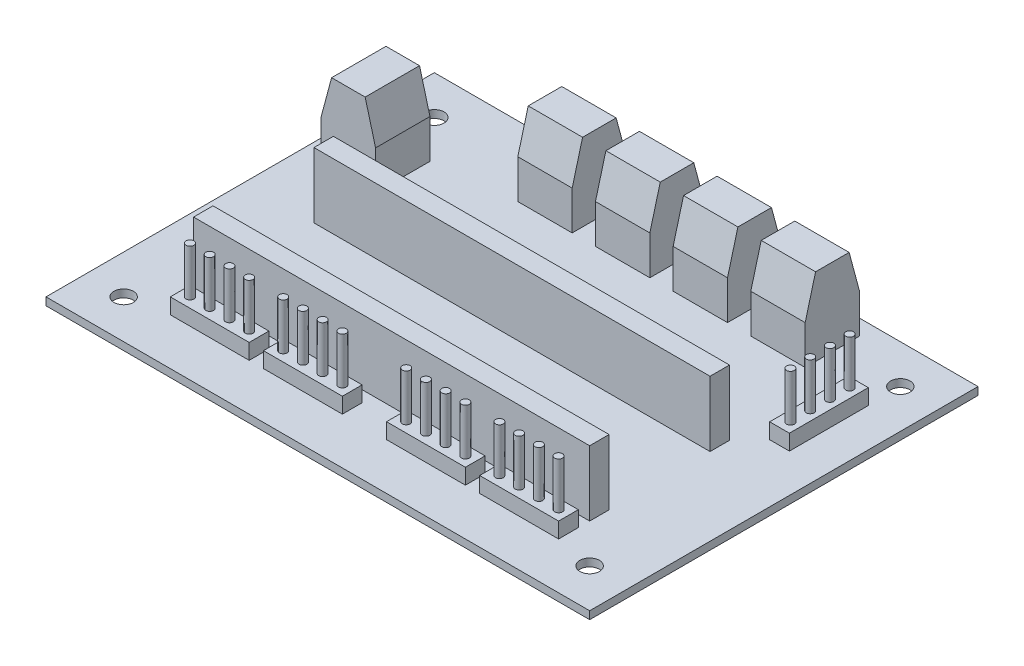
SolidWorks part; units mm, degrees
material "ABS"
ref_plane "Спереди" through (0, 0, 0) normal (0, 0, 1) x (1, 0, 0)
ref_plane "Сверху" through (0, 0, 0) normal (0, 1, 0) x (1, 0, 0)
ref_plane "Справа" through (0, 0, 0) normal (1, 0, 0) x (0, 0, -1)
sketch "Эскиз2" plane through (0, 0, 0) normal (0, 1, 0) x (1, 0, 0)
  line L0 (0, 25) -> (113.3637, 25) construction
  line L1 (0, 0) -> (70, 0)
  line L2 (0, 0) -> (0, 50)
  line L3 (0, 50) -> (70, 50)
  line L4 (70, 0) -> (70, 50)
  line L5 (35, 50) -> (35, -7.1391) construction
  circle A0 centre (5, 45) radius 1.25
  circle A1 centre (65, 45) radius 1.25
  circle A2 centre (65, 5) radius 1.25
  circle A3 centre (5, 5) radius 1.25
  dimension "D3" = 2.5
  dimension "D1" = 70
  dimension "D2" = 50
  dimension "D4" = 5
  dimension "D5" = 5
extrude "Бобышка-Вытянуть1" add sketch "Эскиз2" along normal blind 1
sketch "Эскиз3" plane through (0, 1, 0) normal (0, 1, 0) x (1, 0, 0)
  line L0 (0, 0) -> (70, 0) construction
  line L1 (9, 12.5) -> (60, 12.5)
  line L2 (9, 12.5) -> (9, 10)
  line L3 (9, 10) -> (60, 10)
  line L4 (60, 12.5) -> (60, 10)
  line L9 (70, 0) -> (70, 50) construction
  line L10 (60, 12.5) -> (60, 19) construction
  line L11 (60, 19) -> (7.0253, 19) construction
  line L12 (9, 28) -> (60, 28)
  line L13 (60, 25.5) -> (60, 28)
  line L14 (9, 25.5) -> (60, 25.5)
  line L15 (9, 25.5) -> (9, 28)
  dimension "D1" = 2.5
  dimension "D2" = 51
  dimension "D6" = 10
  dimension "D7" = 10
extrude "Бобышка-Вытянуть2" add sketch "Эскиз3" along normal blind 8.4
sketch "Эскиз4" plane through (0, 1, 0) normal (0, 1, 0) x (1, 0, 0)
  line L0 (70, 0) -> (70, 50) construction
  line L1 (60, 8.54) -> (49.84, 8.54)
  line L2 (60, 8.54) -> (60, 6)
  line L3 (60, 6) -> (49.84, 6)
  line L4 (49.84, 8.54) -> (49.84, 6)
  line L5 (0, 0) -> (70, 0) construction
  line L6 (48, 8.54) -> (48, 6)
  line L7 (35, 0) -> (35, 38.4524) construction
  line L8 (48, 8.54) -> (37.84, 8.54)
  line L9 (37.84, 8.54) -> (37.84, 6)
  line L10 (48, 6) -> (37.84, 6)
  line L11 (10, 6) -> (20.16, 6)
  line L12 (20.16, 8.54) -> (20.16, 6)
  line L13 (10, 8.54) -> (20.16, 8.54)
  line L14 (10, 8.54) -> (10, 6)
  line L15 (22, 8.54) -> (32.16, 8.54)
  line L16 (32.16, 8.54) -> (32.16, 6)
  line L17 (22, 6) -> (32.16, 6)
  line L18 (22, 8.54) -> (22, 6)
  line L19 (62.5185, 40.8177) -> (62.5185, 30.6577)
  line L20 (62.5185, 40.8177) -> (65.0585, 40.8177)
  line L21 (65.0585, 40.8177) -> (65.0585, 30.6577)
  line L22 (62.5185, 30.6577) -> (65.0585, 30.6577)
  dimension "D1" = 2.54
  dimension "D2" = 10.16
  dimension "D3" = 10
  dimension "D4" = 6
  dimension "D5" = 2
extrude "Бобышка-Вытянуть3" add sketch "Эскиз4" along normal blind 2
sketch "Эскиз5" plane through (0, 3, 0) normal (0, 1, 0) x (1, 0, 0)
  line L0 (60, 6) -> (60, 8.54) construction
  line L1 (49.84, 6) -> (60, 6) construction
  line L2 (35, 0) -> (35, 20.127) construction
  line L3 (0, 0) -> (70, 0) construction
  circle A0 centre (58.73, 7.27) radius 0.5
  circle A1 centre (56.19, 7.27) radius 0.5
  circle A2 centre (53.65, 7.27) radius 0.5
  circle A3 centre (51.11, 7.27) radius 0.5
  circle A4 centre (46.73, 7.27) radius 0.5
  circle A5 centre (44.19, 7.27) radius 0.5
  circle A6 centre (41.65, 7.27) radius 0.5
  circle A7 centre (39.11, 7.27) radius 0.5
  circle A8 centre (25.81, 7.27) radius 0.5
  circle A9 centre (11.27, 7.27) radius 0.5
  circle A10 centre (13.81, 7.27) radius 0.5
  circle A11 centre (16.35, 7.27) radius 0.5
  circle A12 centre (18.89, 7.27) radius 0.5
  circle A13 centre (23.27, 7.27) radius 0.5
  circle A14 centre (28.35, 7.27) radius 0.5
  circle A15 centre (30.89, 7.27) radius 0.5
  circle A16 centre (63.8839, 31.9731) radius 0.5
  circle A17 centre (63.8839, 34.5131) radius 0.5
  circle A18 centre (63.8839, 37.0531) radius 0.5
  circle A19 centre (63.8839, 39.5931) radius 0.5
  dimension "D1" = 1
  dimension "D2" = 1.27
  dimension "D3" = 1.27
  dimension "D4" = 4
  dimension "D5" = 2
  dimension "D6" = 4
extrude "Бобышка-Вытянуть4" add sketch "Эскиз5" along normal blind 6
sketch "Эскиз6" plane through (0, 1, 0) normal (0, 1, 0) x (1, 0, 0)
  line L0 (19.7472, 48.0002) -> (26.7472, 48.0002)
  line L5 (2.608, 39.8256) -> (9.608, 39.8256)
  line L6 (2.608, 39.8256) -> (2.608, 32.8256)
  line L7 (2.608, 32.8256) -> (9.608, 32.8256)
  line L8 (9.608, 39.8256) -> (9.608, 32.8256)
  line L9 (19.7472, 48.0002) -> (19.7472, 41.0002)
  line L10 (19.7472, 41.0002) -> (26.7472, 41.0002)
  line L11 (26.7472, 48.0002) -> (26.7472, 41.0002)
  line L12 (29.7472, 48.0002) -> (36.7472, 48.0002)
  line L13 (36.7472, 48.0002) -> (36.7472, 41.0002)
  line L14 (29.7472, 41.0002) -> (36.7472, 41.0002)
  line L15 (29.7472, 48.0002) -> (29.7472, 41.0002)
  line L16 (39.7472, 48.0002) -> (46.7472, 48.0002)
  line L17 (46.7472, 48.0002) -> (46.7472, 41.0002)
  line L18 (39.7472, 41.0002) -> (46.7472, 41.0002)
  line L19 (39.7472, 48.0002) -> (39.7472, 41.0002)
  line L20 (49.7472, 48.0002) -> (56.7472, 48.0002)
  line L21 (56.7472, 48.0002) -> (56.7472, 41.0002)
  line L22 (49.7472, 41.0002) -> (56.7472, 41.0002)
  line L23 (49.7472, 48.0002) -> (49.7472, 41.0002)
  dimension "D1" = 7
  dimension "D2" = 7
  dimension "D3" = 4
extrude "Бобышка-Вытянуть5" add sketch "Эскиз6" along normal blind 10
chamfer "Фаска1" distance 5 angle 15 10 edges at (53.2472, 11, -48.0002) (53.2472, 11, -41.0002) (43.2472, 11, -48.0002) (43.2472, 11, -41.0002) (33.2472, 11, -41.0002) (33.2472, 11, -48.0002) (23.2472, 11, -48.0002) (23.2472, 11, -41.0002) (9.608, 11, -36.3256) (2.608, 11, -36.3256) first distance on face at (53.2472, 6, -48.0002) first distance on face at (53.2472, 6, -41.0002) first distance on face at (43.2472, 6, -48.0002) first distance on face at (43.2472, 6, -41.0002) first distance on face at (33.2472, 6, -41.0002) first distance on face at (33.2472, 6, -48.0002) first distance on face at (23.2472, 6, -48.0002) first distance on face at (23.2472, 6, -41.0002) first distance on face at (9.608, 6, -36.3256) first distance on face at (2.608, 6, -36.3256)
